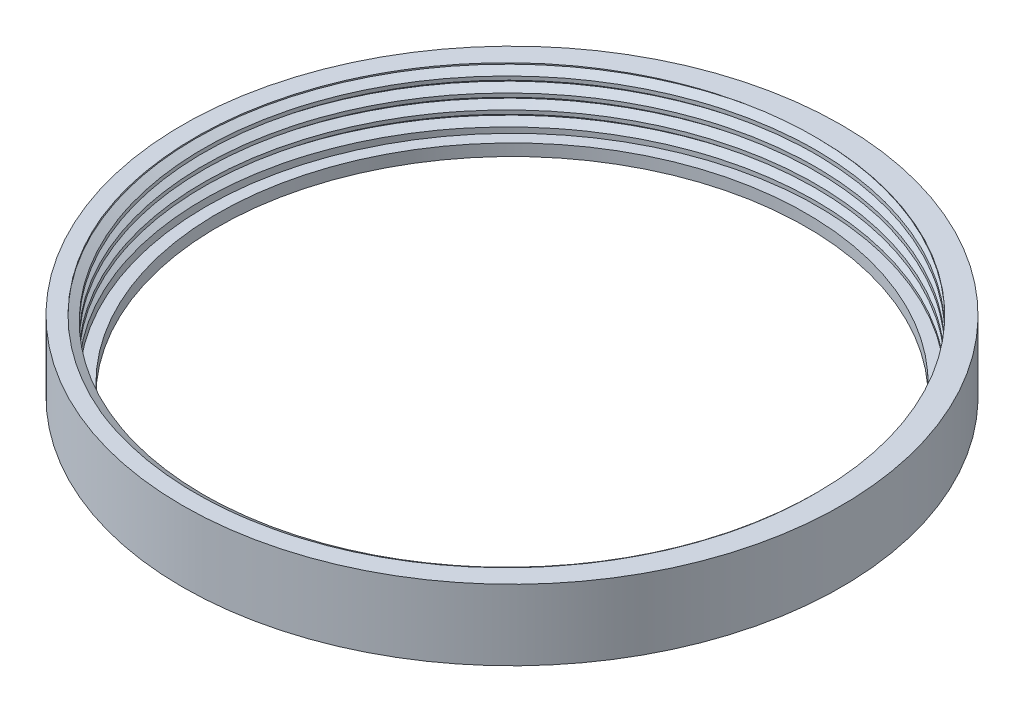
SolidWorks part; units mm, degrees
ref_plane "Front Plane" through (0, 0, 0) normal (0, 0, 1) x (1, 0, 0)
ref_plane "Top Plane" through (0, 0, 0) normal (0, 1, 0) x (1, 0, 0)
ref_plane "Right Plane" through (0, 0, 0) normal (1, 0, 0) x (0, 0, -1)
sketch "Sketch1" plane through (0, 0, 0) normal (0, 1, 0) x (1, 0, 0)
  circle A0 centre (0, 0) radius 50
  circle A1 centre (0, 0) radius 52
  circle A2 centre (0, 0) radius 56
extrude "Boss-Extrude1" add sketch "Sketch1" along normal blind 2 contours A1 A0 | A2 A1 region at (-50.5292, 0, 0) region at (-54.4161, 0, 0)
extrude "Boss-Extrude2" add sketch "Sketch1<7>" along normal blind 12 contours A2 A1 region at (-54.4161, 0, 0)
sketch "Sketch1<7>" plane through (0, 0, 0) normal (0, 1, 0) x (1, 0, 0) same geometry as "Sketch1"
thread "Thread2" pitch 2.5 method cut profile "Thread Profile2" start angle 0, offset 0, length 0, pitch 2.5, diameter 104
ref_plane "Plane2" through (52, 2, 0) normal (0, 0, 1) x (1, 0, 0)
sketch "Thread Profile2" plane through (52, 2, 0) normal (0, 0, 1) x (1, 0, 0)
  line L0 (0, 0) -> (0, 2.5) construction
  line L1 (0, 0) -> (1.3532, 0.7812)
  line L2 (1.3532, 0.7812) -> (1.3532, 1.0937)
  line L3 (1.3532, 1.0937) -> (0, 1.875)
  line L4 (1.3532, 0.9375) -> (0, 0.9375) construction
  line L11 (0, 0) -> (0, 1.875)
  point P2 (0, 0)
  dimension "Pitch" = 2.5
  dimension "Profile_Angle" = 60
  dimension "Profile_Land" = 0.3125
  dimension "Profile_Height" = 1.3532
